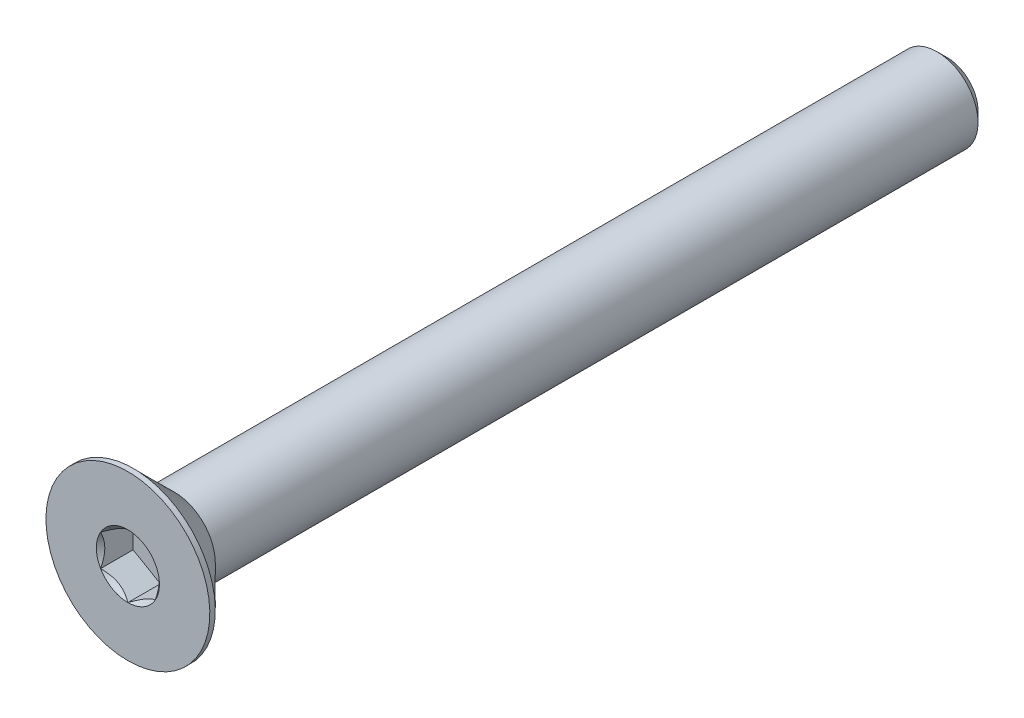
SolidWorks part; units mm, degrees
material "Alloy Steel"
ref_plane "Front" through (0, 0, 0) normal (0, 0, 1) x (1, 0, 0)
ref_plane "Top" through (0, 0, 0) normal (0, 1, 0) x (1, 0, 0)
ref_plane "Right" through (0, 0, 0) normal (1, 0, 0) x (0, 0, -1)
sketch "Sketch1" plane through (0, 0, 0) normal (1, 0, 0) x (0, 0, -1)
  line L0 (0, 3) -> (0.2, 3) construction
  line L1 (0.2, 3) -> (1.7, 1.5) construction
  line L2 (0, 1.5) -> (30, 1.5)
  line L3 (30, 1.5) -> (30, 0)
  line L4 (30, 0) -> (0, 0)
  line L5 (0, 0) -> (0, 3) construction
  line L6 (0, 3) -> (0, -3) construction
  line L7 (30, 1.5) -> (30, -1.5) construction
  line L8 (0, -3) -> (0.2, -3) construction
  line L9 (0.2, -3) -> (1.7, -1.5) construction
  line L11 (0, 1.5) -> (0, 0)
  line L12 (1.7, 1.5) -> (1.7, 0) construction
revolve "Revolve1" add sketch "Sketch1" angle 360 mid plane about L4
sketch "Sketch3" plane through (0, 0, -30) normal (0, 0, -1) x (-1, 0, 0)
  circle A0 centre (0, 0) radius 1.5
curve "Helix/Spiral1" pitch 0.5 height 30 turns 60
sketch "Sketch2" plane through (0, 0, 0) normal (1, 0, 0) x (0, 0, -1)
  line L0 (30, 1.5) -> (30.4375, 1.5)
  line L1 (30.4375, 1.5) -> (30.25, 1.1752)
  line L2 (30.25, 1.1752) -> (30.1875, 1.1752)
  line L3 (30.1875, 1.1752) -> (30, 1.5)
  line L4 (30.0938, 1.3376) -> (30.3438, 1.3376) construction
  dimension "D1" = 60
  dimension "D2" = 0.0625
  dimension "D3" = 0.25
chamfer "Chamfer1" distance 0.375 angle 45 1 edges at (0, 1.5, -30)
sweep "Cut-Sweep1" [suppressed] cut profiles "Sketch2" path "Helix/Spiral1"
sketch "Sketch7" plane through (0, 0, 0) normal (1, 0, 0) x (0, 0, -1)
  line L0 (0, 3) -> (0.2, 3) construction
  line L1 (0.2, 3) -> (1.7, 1.5) construction
  line L2 (0, 3) -> (0.2, 3)
  line L3 (0.2, 3) -> (1.7, 1.5)
  line L4 (1.7, 1.5) -> (1.7, 0) construction
  line L5 (1.7, 1.5) -> (1.7, 0)
  line L7 (0, 0) -> (0, 3) construction
  line L8 (0, 0) -> (0, 3)
  line L9 (0, 0) -> (1.7, 0)
  line L10 (3.3, 0) -> (-3.3, 0) construction
revolve "Revolve2" add sketch "Sketch7" angle 360 mid plane about L9
ref_plane "Plane1" through (0, 0, -1.7) normal (0, 0, 1) x (1, 0, 0)
sketch "Sketch8" plane through (0, 0, -1.7) normal (0, 0, 1) x (1, 0, 0)
  circle A0 centre (0, 0) radius 1.5
extrude "Boss-Extrude1" add sketch "Sketch8" against normal through all draft 45
sketch "Sketch5" plane through (0, 0, 0) normal (0, 0, 1) x (1, 0, 0)
  line L1 (1, -0.5774) -> (1, 0.5774)
  line L2 (1, 0.5774) -> (0, 1.1547)
  line L3 (0, 1.1547) -> (-1, 0.5774)
  line L4 (-1, 0.5774) -> (-1, -0.5774)
  line L5 (-1, -0.5774) -> (0, -1.1547)
  line L6 (0, -1.1547) -> (1, -0.5774)
  circle A0 centre (0, 0) radius 1 construction
  dimension "Hex" = 2
extrude "Cut-Extrude2" cut sketch "Sketch5" against normal blind 1.19
sketch "Sketch6" plane through (0, 0, 0) normal (0, 0, 1) x (1, 0, 0)
  circle A0 centre (0, 0) radius 1.1547
extrude "Cut-Extrude3" cut sketch "Sketch6" against normal blind 1.19 draft 45
sketch "Sketch9" [suppressed] plane through (0, 0, -1.5) normal (0, 0, 1) x (1, 0, 0)
  circle A1 centre (0, 0) radius 1.25
  circle A2 centre (0, 0) radius 1.25
  point P0 (0, 1.25)
  dimension "D1" = 0
extrude "Boss-Extrude2" [suppressed] add sketch "Sketch9" against normal offset from surface (3.5 mm away) 26 up to face at (0, 1.125, -30)
fillet "Fillet1" [suppressed] radius 0.3
sketch "Sketch10" plane through (0, 0, 0) normal (1, 0, 0) x (0, 0, -1)
  line L0 (30, 1.5) -> (30, -1.5) construction
  point P0 (29.25, -1.5)
  dimension "D1" = 0.75
equation "\"D3@Helix/Spiral1\" = \"Lg@Sketch1\""
equation "\"D2@Sketch2\" = \"D4@Helix/Spiral1\" * .125"
equation "\"D3@Sketch2\" = \"D4@Helix/Spiral1\" * .5"
equation "\"D1@Chamfer1\" = \"D4@Helix/Spiral1\" * .75"
equation "\"D1@Cut-Extrude2\" = \"Head Ht@Sketch1\" * .7"
equation "\"D1@Sketch10\" = \"D4@Helix/Spiral1\" * 1.5"
equation "\"D1@Cut-Extrude3\" = \"D1@Cut-Extrude2\""
equation "\"D1@Fillet1\" = \"Dia@Sketch1\" * .1"
